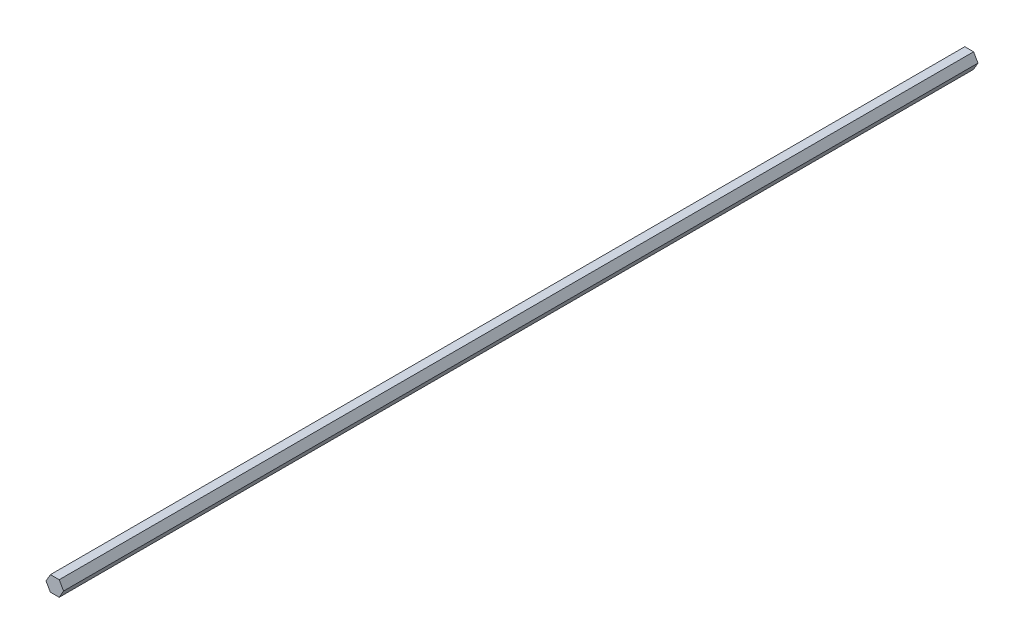
SolidWorks part; units mm, degrees
material "1060 Alloy"
ref_plane "Front Plane" through (0, 0, 0) normal (0, 0, 1) x (1, 0, 0)
ref_plane "Top Plane" through (0, 0, 0) normal (0, 1, 0) x (1, 0, 0)
ref_plane "Right Plane" through (0, 0, 0) normal (1, 0, 0) x (0, 0, -1)
sketch "Sketch1" plane through (0, 0, 0) normal (0, 0, 1) x (1, 0, 0)
  line L1 (3.6761, -6.3443) -> (7.3323, 0.0115)
  line L2 (7.3323, 0.0115) -> (3.6562, 6.3557)
  line L3 (3.6562, 6.3557) -> (-3.6761, 6.3443)
  line L4 (-3.6761, 6.3443) -> (-7.3323, -0.0115)
  line L5 (-7.3323, -0.0115) -> (-3.6562, -6.3557)
  line L6 (-3.6562, -6.3557) -> (3.6761, -6.3443)
  circle A0 centre (0, 0) radius 6.35 construction
  dimension "D1" = 12.7
extrude "Boss-Extrude1" add sketch "Sketch1" along normal blind 762
